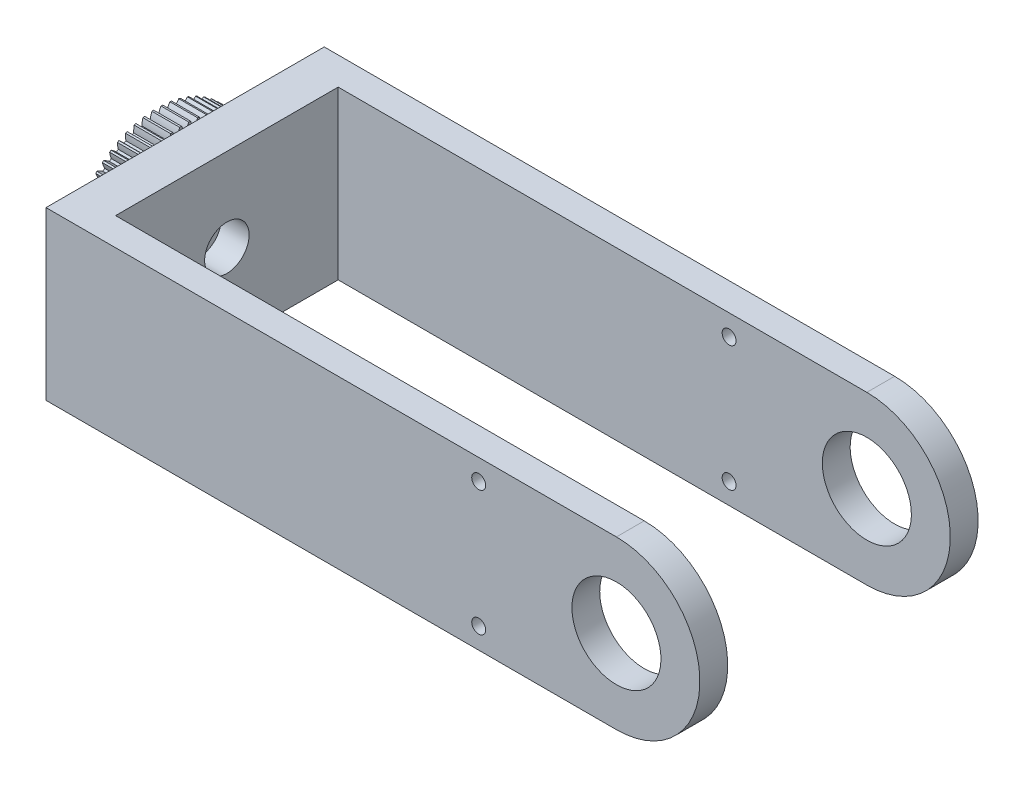
SolidWorks part; units mm, degrees
ref_plane "Plane1" through (0, 0, 0) normal (0, 0, 1) x (1, 0, 0)
ref_plane "Plane2" through (0, 0, 0) normal (0, 1, 0) x (1, 0, 0)
ref_plane "Plane3" through (0, 0, 0) normal (1, 0, 0) x (0, 0, -1)
other "Configuration Table"
sketch "HoldingSke" plane through (0, 0, 0) normal (0, 1, 0) x (1, 0, 0)
  line L0 (0, 0) -> (0.5, -0.866)
  line L1 (-15, 0) -> (100, 0) construction
  line L2 (0, 0) -> (-2.1039, 2.3779)
  line L3 (0, 0) -> (-11.863, 4.5341)
  line L4 (0, 0) -> (4.318, 7.479)
  line L5 (0, 0) -> (-46.8476, -17.4728)
  line L6 (0, 0) -> (-20.7241, -13.9826)
  line L7 (-2.1039, 2.3779) -> (8.6586, 51.2059)
  line L8 (-76.2, 54.61) -> (-74.4, 54.61)
  line L9 (-71.009, 38.7566) -> (-53.1078, 45.2721)
  line L10 (-76.2, 71.12) -> (104.1128, 71.12)
  line L11 (0, 0) -> (-25, 0)
  line L12 (-76.2, 101.6) -> (-76.162, 101.6)
  line L13 (24.9733, 27.94) -> (52.9518, 28.4284)
  line L14 (24.9733, 27.94) -> (24.9743, 27.94)
  line L15 (24.9733, 27.94) -> (100.4006, 29.5858)
  line L16 (-63.627, -1) -> (-12.827, -1)
  circle A0 centre (0, 0) radius 5
  circle A1 centre (0, 0) radius 28.749
  circle A2 centre (0, 0) radius 37.5
  circle A3 centre (0, 0) radius 5
  dimension "MHD" = 57.498
  dimension "Hub_dia" = 75
  dimension "Bore" = 10
  dimension "MBD" = 10
  dimension "Num_teeth" = 60
  dimension "Pitch" = 1
  dimension "Overall_len" = 50
  dimension "Show_teeth" = 60
  dimension "Thickness" = 25
  dimension "OAL" = 50.0001
  dimension "T_dim" = 1.8
  dimension "Ap" = 20
  dimension "H" = 19.05
  dimension "Pitch_radius" = 180.3128
  dimension "Width" = 25
  dimension "Backlash" = 0.038
  dimension "Addendum_fac" = 1
  dimension "Dedendum_fac" = 1.25
  dimension "Clearance_fac" = 0.25
  dimension "Dedendum_add" = 0.001
  dimension "Module" = 1
sketch "BasProSke" plane through (0, 0, 0) normal (0, 1, 0) x (1, 0, 0)
  line L0 (-10, 0) -> (60, 0) construction
  line L1 (0, 0) -> (0, 31)
  line L2 (0, 0) -> (25, 0)
  line L3 (25, 0) -> (25, 31)
  line L4 (25, 31) -> (0, 31)
  dimension "Thickness" = 25
  dimension "Diameter" = 62
revolve "Base-Revolve" add sketch "BasProSke" angle 360 about L0
sketch "TooCutSke" plane through (0, 0, 0) normal (1, 0, 0) x (0, 0, -1)
  line L1 (0, 0) -> (0, 107) construction
  line L2 (0, 0) -> (-0.8518, 29.9879) construction
  line L3 (0, 0) -> (-3.1393, 59.9006) construction
  line L4 (-0.8518, 29.9879) -> (-1.5696, 29.9503) construction
  arc A0 (0.4302, 28.7458) -> (-0.4302, 28.7458) centre (0, 0) ccw
  arc A1 (1.3127, 30.9976) -> (-1.3127, 30.9976) centre (0, 0) ccw
  circle A2 centre (0, 0) radius 30 construction
  circle A3 centre (0, 0) radius 28.1908 construction
  arc A4 (-0.4302, 28.7458) -> (-1.3127, 30.9976) centre (-11.9871, 25.5153) ccw
  arc A5 (1.3127, 30.9976) -> (0.4302, 28.7458) centre (11.9871, 25.5153) ccw
  dimension "Root_dia" = 57.498
  dimension "Overcut_dia" = 62.0508
  dimension "Pitch_dia" = 60
  dimension "Base_dia" = 56.3816
  dimension "Flank_rad" = 12
  dimension "Half_ang" = 3
  dimension "Half_CT" = 0.7188
extrude "ToothCut" cut sketch "TooCutSke" along normal through all
fillet "Breaks" [suppressed] radius 0.02 tangent propagation no
fillet "RootFillets" [suppressed] radius 0.251
pattern_circular "TeethCuts" count 60 every 6 about axis through (-10, 0, 0) along (1, 0, 0) of "ToothCut", "RootFillets", "Breaks"
sketch "HubNeaOneSke" plane through (0, 0, 0) normal (-1, 0, 0) x (0, 0, 1)
  circle A0 centre (0, 0) radius 28.749
  dimension "Diameter" = 57.498
extrude "HubNearOne" [suppressed] add sketch "HubNeaOneSke" along normal blind 25.0001
sketch "HubNeaBotSke" plane through (0, 0, 0) normal (-1, 0, 0) x (0, 0, 1)
  circle A0 centre (0, 0) radius 28.749
  dimension "Diameter" = 57.498
extrude "HubNearBoth" [suppressed] add sketch "HubNeaBotSke" along normal blind 12.5
ref_plane "FarPln" through (25, 0, 0) normal (1, 0, 0) x (0, 0, -1)
sketch "HubFarSke" plane through (25, 0, 0) normal (1, 0, 0) x (0, 0, -1)
  circle A0 centre (0, 0) radius 28.749
  dimension "Diameter" = 57.498
extrude "HubFar" [suppressed] add sketch "HubFarSke" along normal blind 12.5
sketch "BorSke" plane through (0, 0, 0) normal (1, 0, 0) x (0, 0, -1)
  circle A0 centre (0, 0) radius 5
  dimension "Diameter" = 10
extrude "Bore" cut sketch "BorSke" along normal mid plane 100.0001
sketch "KeySke" plane through (0, 0, 0) normal (1, 0, 0) x (0, 0, -1)
  line L0 (-2, 0) -> (-2, 6.8)
  line L1 (-2, 6.8) -> (2, 6.8)
  line L2 (2, 6.8) -> (2, 0)
  line L3 (0, 0) -> (0, 34) construction
  line L4 (-2, 0) -> (2, 0)
  dimension "Offset" = 6.8
  dimension "Width" = 4
extrude "Keyway" [suppressed] cut sketch "KeySke" along normal mid plane 100.0001
pattern_circular "Keyway2" [suppressed] count 2 every 90 about axis through (-10, 0, 0) along (1, 0, 0) reverse direction yes
sketch "Sketch4" plane through (25, 0, 0) normal (1, 0, 0) x (0, 0, -1)
  line L1 (-50, 30) -> (50, 30)
  line L2 (-50, 30) -> (-50, -30)
  line L3 (-50, -30) -> (50, -30)
  line L4 (50, 30) -> (50, -30)
  line L5 (-50, 30) -> (50, -30) construction
  line L6 (-50, -30) -> (50, 30) construction
  point P0 (0, 0)
  dimension "D1" = 100
  dimension "D2" = 60
extrude "Boss-Extrude2" add sketch "Sketch4" along normal blind 15
sketch "Sketch6" plane through (40, 0, 0) normal (1, 0, 0) x (0, 0, -1)
  line L0 (-50, -30) -> (50, -30) construction
  line L1 (-50, 30) -> (-40, 30)
  line L2 (-50, 30) -> (-50, -30)
  line L3 (-50, -30) -> (-40, -30)
  line L4 (-40, 30) -> (-40, -30)
  line L6 (50, 30) -> (40, 30)
  line L7 (50, 30) -> (50, -30)
  line L8 (50, -30) -> (40, -30)
  line L9 (40, 30) -> (40, -30)
  dimension "D1" = 10
extrude "Boss-Extrude3" add sketch "Sketch6" along normal blind 220
sketch "Sketch7" plane through (0, 0, 0) normal (-1, 0, 0) x (0, 0, 1)
  circle A0 centre (0, 0) radius 46.2966
extrude "Cut-Extrude1" cut sketch "Sketch7" against normal blind 15
sketch "Sketch8" plane through (15, 0, 0) normal (-1, 0, 0) x (0, 0, 1)
  circle A0 centre (0, 0) radius 10
  circle A1 centre (0, 0) radius 5 construction
  circle A2 centre (0, 0) radius 5
  dimension "D1" = 20
extrude "Boss-Extrude4" add sketch "Sketch8" along normal blind 1
sketch "Sketch9" plane through (14, 0, 0) normal (-1, 0, 0) x (0, 0, 1)
  circle A0 centre (0, 0) radius 5
  dimension "D1" = 10
extrude "Cut-Extrude2" cut sketch "Sketch9" against normal through all
sketch "Sketch10" plane through (15, 0, 0) normal (-1, 0, 0) x (0, 0, 1)
  circle A0 centre (0, 0) radius 30
  dimension "D1" = 60
fillet "Fillet1" 2 edges at (260, 30, -45) (260, -30, -45) type full round first side face at (73.5, 30, 0) second side face at (73.5, -30, 0) middle face at (260, 0, -45)
fillet "Fillet2" 2 edges at (260, 30, 45) (260, -30, 45) type full round first side face at (70.5, 30, 0) second side face at (70.5, -30, 0) middle face at (260, 0, 45)
sketch "Sketch11" plane through (0, 0, -50) normal (0, 0, -1) x (-1, 0, 0)
  circle A0 centre (-230, 0) radius 16
  dimension "D1" = 32
extrude "Cut-Extrude3" cut sketch "Sketch11" against normal through all
sketch "Sketch12" plane through (40, 0, 0) normal (1, 0, 0) x (0, 0, -1)
  circle A0 centre (0, 0) radius 8
  dimension "D1" = 16
extrude "Cut-Extrude4" cut sketch "Sketch12" against normal blind 10
sketch "Sketch13" plane through (0, 0, -50) normal (0, 0, -1) x (-1, 0, 0)
  line L0 (-180.5, -22.5) -> (-180.5, 22.5) construction
  line L1 (-230, 30) -> (-25, 30) construction
  circle A0 centre (-180.5, 22.5) radius 2.5
  circle A1 centre (-180.5, -22.5) radius 2.5
  circle A2 centre (-230, 0) radius 16 construction
  point P6 (-180.5, 0)
  dimension "D1" = 49.5
  dimension "D2" = 5
  dimension "D3" = 45
  dimension "D4" = 30
extrude "Cut-Extrude5" cut sketch "Sketch13" against normal through all
equation "' \"Module@HoldingSke\" = 6.35"
equation "' \"Num_teeth@HoldingSke\" = 12"
equation "' \"Ap@HoldingSke\" =  20"
equation "' \"Ap@HoldingSke\" = 20"
equation "' \"Width@HoldingSke\" = 0.5 * 25.4"
equation "' \"Hub_dia@HoldingSke\"= 1 * 25.4"
equation "' \"Hub_dia@HoldingSke\" = 1 * 25.4"
equation "' \"Overall_len@HoldingSke\" = 1.0 * 25.4"
equation "' \"Bore@HoldingSke\" = 0.75 * 25.4"
equation "' \"T_dim@HoldingSke\" = 0.1 * 25.4"
equation "' \"Width@KeySke\" = 0.25 * 25.4"
equation "' \"Show_teeth@HoldingSke\" = 13"
equation "' \"Backlash@HoldingSke\" = 0.009 * 25.4"
equation "' \"Addendum_fac@HoldingSke\" = 1.0"
equation "' \"Dedendum_fac@HoldingSke\" = 1.25"
equation "' \"Dedendum_add@HoldingSke\" = 0.00005 * 25.4"
equation "' \"Clearance_fac@HoldingSke\" = 0.25"
equation "\"Pitch@HoldingSke\" = 1 / \"Module@HoldingSke\""
equation "\"Overcut_dia@TooCutSke\" = (\"Num_teeth@HoldingSke\" + 2 * \"Addendum_fac@HoldingSke\") / \"Pitch@HoldingSke\" + 0.002 * 25.4"
equation "\"Pitch_dia@TooCutSke\" = \"Num_teeth@HoldingSke\" / \"Pitch@HoldingSke\""
equation "\"Base_dia@TooCutSke\" = \"Num_teeth@HoldingSke\" / \"Pitch@HoldingSke\" * cos((\"Ap@HoldingSke\"  * 3.14159265 / 180))"
equation "\"Root_dia@TooCutSke\" = (\"Num_teeth@HoldingSke\" + 2) / \"Pitch@HoldingSke\" - 2 * (\"Addendum_fac@HoldingSke\" + \"Dedendum_fac@HoldingSke\") / \"Pitch@HoldingSke\" - \"Dedendum_add@HoldingSke\" * 2"
equation "\"Half_ang@TooCutSke\" = 180 / \"Num_teeth@HoldingSke\""
equation "\"Half_CT@TooCutSke\" = \"Num_teeth@HoldingSke\" / \"Pitch@HoldingSke\" * sin((3.14159265 / 2 / \"Num_teeth@HoldingSke\")) / 2 - 7 * \"Backlash@HoldingSke\" / 4"
equation "\"Flank_rad@TooCutSke\" = \"Num_teeth@HoldingSke\" / \"Pitch@HoldingSke\" / 5"
equation "\"Radius@RootFillets\" = \"Clearance_fac@HoldingSke\" / \"Pitch@HoldingSke\" + \"Dedendum_add@HoldingSke\""
equation "\"Break_rad@Breaks\" = 0.02 / \"Pitch@HoldingSke\""
equation "\"Thickness@HoldingSke\" = \"Width@HoldingSke\""
equation "\"OAL@HoldingSke\" = \"Thickness@HoldingSke\""
equation "\"MHD@HoldingSke\" = (\"Num_teeth@HoldingSke\" + 2) / \"Pitch@HoldingSke\" - 2 * (\"Addendum_fac@HoldingSke\" + \"Dedendum_fac@HoldingSke\")  / \"Pitch@HoldingSke\" - \"Dedendum_add@HoldingSke\" * 2"
equation "\"MBD@HoldingSke\" = (\"Num_teeth@HoldingSke\" + 2) / \"Pitch@HoldingSke\" - 2 * (\"Addendum_fac@HoldingSke\" + \"Dedendum_fac@HoldingSke\")  / \"Pitch@HoldingSke\" - \"Dedendum_add@HoldingSke\" * 2 - 0.002 * 25.4"
equation "\"MHD@HoldingSke\" = ((sgn( \"MHD@HoldingSke\" - \"Hub_dia@HoldingSke\" )-1)*( \"MHD@HoldingSke\" - \"Hub_dia@HoldingSke\" ))/-2+ \"Hub_dia@HoldingSke\""
equation "\"MBD@HoldingSke\" = ((sgn( \"MBD@HoldingSke\" - \"Bore@HoldingSke\" )-1)*( \"MBD@HoldingSke\" - \"Bore@HoldingSke\" ))/-2+ \"Bore@HoldingSke\""
equation "\"OAL@HoldingSke\" = ((sgn( \"OAL@HoldingSke\" - \"Overall_len@HoldingSke\" )+1)*( \"OAL@HoldingSke\" - \"Overall_len@HoldingSke\" ))/2 + \"Overall_len@HoldingSke\" + 0.000002 * 25.4"
equation "\"Num_teeth@TeethCuts\" = int( \"Show_teeth@HoldingSke\" ) + 1"
equation "\"Num_teeth@TeethCuts\" = ((sgn( \"Num_teeth@TeethCuts\" - \"Num_teeth@HoldingSke\" )-1)*( \"Num_teeth@TeethCuts\" - \"Num_teeth@HoldingSke\" ))/-2+ \"Num_teeth@HoldingSke\""
equation "\"Num_teeth@TeethCuts\" = ((sgn( \"Num_teeth@TeethCuts\" - 2.0)+1)*( \"Num_teeth@TeethCuts\" - 2.0))/2 +2.0"
equation "\"Angle@TeethCuts\" = 360.0 / \"Num_teeth@HoldingSke\""
equation "\"Diameter@BasProSke\" = (\"Num_teeth@HoldingSke\" + 2 * \"Addendum_fac@HoldingSke\") / \"Pitch@HoldingSke\""
equation "\"Thickness@BasProSke\"  = \"Thickness@HoldingSke\""
equation "' \"Fillet_rad@BasProSke\" =  \"Thickness@HoldingSke\" * 0.05"
equation "' \"Fillet_rad@BasProSke\" = \"Thickness@HoldingSke\" * 0.05"
equation "\"MHD@HoldingSke\" = ((sgn( \"MHD@HoldingSke\" - \"Root_dia@TooCutSke\" )-1)*( \"MHD@HoldingSke\" - \"Root_dia@TooCutSke\" ))/-2+ \"Root_dia@TooCutSke\""
equation "\"Diameter@HubNeaOneSke\" = \"MHD@HoldingSke\""
equation "\"Length@HubNearOne\" = \"OAL@HoldingSke\" - \"Thickness@BasProSke\""
equation "\"Diameter@HubNeaBotSke\" = \"MHD@HoldingSke\""
equation "\"Length@HubNearBoth\" = ( \"OAL@HoldingSke\" - \"Thickness@BasProSke\" ) / 2.0"
equation "\"Thickness@FarPln\" = \"Thickness@BasProSke\""
equation "\"Diameter@HubFarSke\" = \"MHD@HoldingSke\""
equation "\"Length@HubFar\" = ( \"OAL@HoldingSke\" - \"Thickness@BasProSke\" ) / 2.0"
equation "\"Diameter@BorSke\" = \"MBD@HoldingSke\""
equation "\"D1@Bore\" = \"OAL@HoldingSke\" * 2.0"
equation "\"D1@Keyway\" = \"OAL@HoldingSke\" * 2.0"
equation "\"Offset@KeySke\" = \"T_dim@HoldingSke\" + \"MBD@HoldingSke\" / 2.0"
